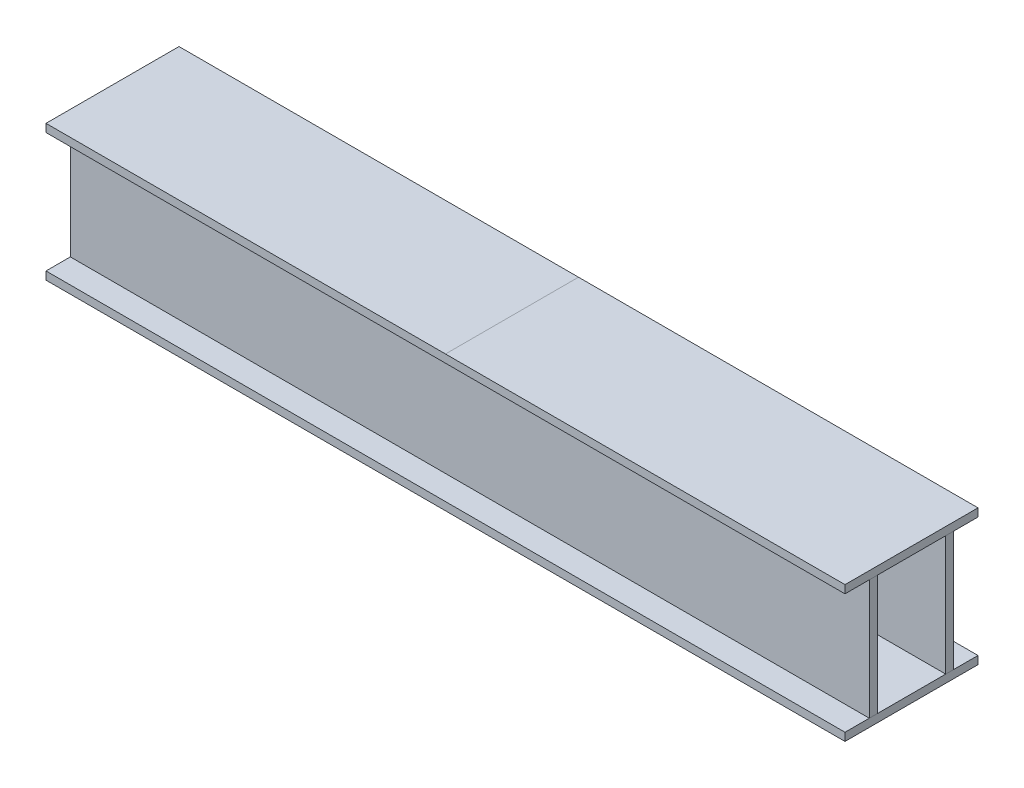
SolidWorks part; units mm, degrees
ref_plane "前视基准面" through (0, 0, 0) normal (0, 0, 1) x (1, 0, 0)
ref_plane "上视基准面" through (0, 0, 0) normal (0, 1, 0) x (1, 0, 0)
ref_plane "右视基准面" through (0, 0, 0) normal (1, 0, 0) x (0, 0, -1)
sketch "草图1" plane through (0, 0, 0) normal (1, 0, 0) x (0, 0, -1)
  line L0 (0, -1000) -> (0, 49000) construction
  line L1 (-1000, 0) -> (49000, 0) construction
  line L3 (-83.228, 85) -> (83.228, 85)
  line L4 (-83.228, 85) -> (-83.228, 75)
  line L5 (-83.228, 75) -> (83.228, 75)
  line L6 (83.228, 85) -> (83.228, 75)
  line L7 (-83.228, 85) -> (83.228, 75) construction
  line L8 (-83.228, 75) -> (83.228, 85) construction
  line L9 (-52.7975, -75) -> (-42.7975, -75)
  line L10 (-52.7975, -75) -> (-52.7975, 75)
  line L11 (-52.7975, 75) -> (-42.7975, 75)
  line L12 (-42.7975, -75) -> (-42.7975, 75)
  line L13 (-52.7975, -75) -> (-42.7975, 75) construction
  line L14 (-52.7975, 75) -> (-42.7975, -75) construction
  line L15 (42.7975, -75) -> (52.7975, -75)
  line L16 (42.7975, -75) -> (42.7975, 75)
  line L17 (42.7975, 75) -> (52.7975, 75)
  line L18 (52.7975, -75) -> (52.7975, 75)
  line L19 (42.7975, -75) -> (52.7975, 75) construction
  line L20 (42.7975, 75) -> (52.7975, -75) construction
  line L21 (-83.228, -85) -> (83.228, -85)
  line L22 (-83.228, -85) -> (-83.228, -75)
  line L23 (-83.228, -75) -> (83.228, -75)
  line L24 (83.228, -85) -> (83.228, -75)
  line L25 (-83.228, -85) -> (83.228, -75) construction
  line L26 (-83.228, -75) -> (83.228, -85) construction
  point P4 (0, 80)
  point P10 (-47.7975, 0)
  point P15 (47.7975, 0)
  point P20 (0, -80)
  dimension "D1" = 166.456
  dimension "D2" = 10
  dimension "D3" = 150
  dimension "D4" = 10
  dimension "D5" = 105.595
  dimension "D6" = 10
extrude "凸台-拉伸1" add sketch "草图1" along normal mid plane 1000 contours L6 L3 L4 L5 | L21 L24 L23 L15 L9 L22 region at (0, 80, 0) region at (0, -80, 0)
extrude "凸台-拉伸2" add sketch "草图1<3>" along normal mid plane 1000 separate body contours L9 L12 L5 L10 | L15 L18 L5 L16 region at (0, 0, 47.7975) region at (0, 0, -47.7975)
sketch "草图1<3>" plane through (0, 0, 0) normal (1, 0, 0) x (0, 0, -1) same geometry as "草图1"
sketch "草图2" plane through (0, 85, 0) normal (0, 1, 0) x (1, 0, 0)
  line L0 (-1000, 0) -> (49000, 0) construction
  line L1 (0, 83.228) -> (0, -83.228)
  line L2 (500, 83.228) -> (-500, 83.228) construction
  line L3 (500, -83.228) -> (-500, -83.228) construction
  line L4 (0, -1000) -> (0, 49000) construction
split line "分割线1"
equation "\"a\"=166.456"
equation "\"D1@草图1\"=\"a\""
equation "\"b\"=10"
equation "\"D2@草图1\"=\"b\""
equation "\"c\"=150"
equation "\"D3@草图1\"=\"c\""
equation "\"d\"=10"
equation "\"D4@草图1\"=\"d\""
equation "\"e\"=105.595"
equation "\"D5@草图1\"=\"e\""
equation "\"f\"=10"
equation "\"D6@草图1\"=\"f\""
equation "\"Long\"= 1000'长度"
equation "\"D1@凸台-拉伸1\"=\"Long\""
equation "\"D1@凸台-拉伸2\"=\"Long\""
